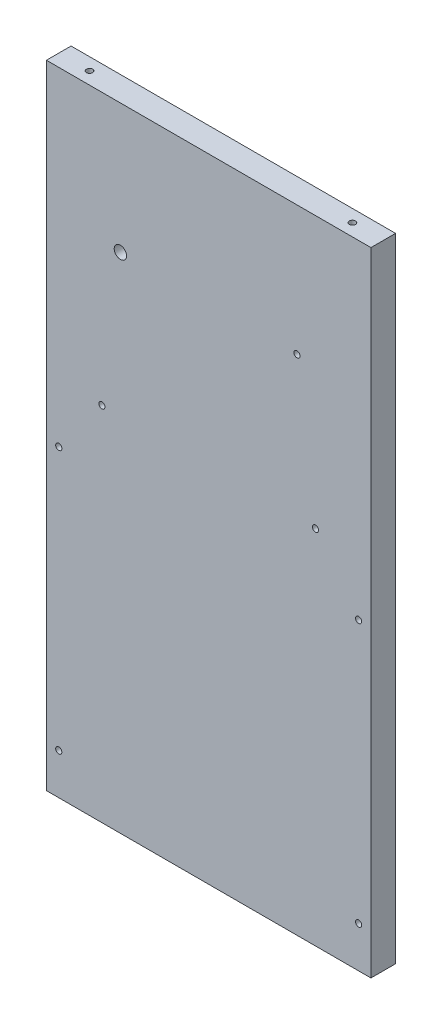
SolidWorks part; units mm, degrees
ref_plane "Front Plane" through (0, 0, 0) normal (0, 0, 1) x (1, 0, 0)
ref_plane "Top Plane" through (0, 0, 0) normal (0, 1, 0) x (1, 0, 0)
ref_plane "Right Plane" through (0, 0, 0) normal (1, 0, 0) x (0, 0, -1)
sketch "Sketch1" plane through (0, 0, 0) normal (0, 0, 1) x (1, 0, 0)
  line L0 (-156.9512, -28.4634) -> (1.0488, -28.4634) construction
  line L1 (-156.9512, 103.5366) -> (1.0488, 103.5366)
  line L2 (-156.9512, 103.5366) -> (-156.9512, -204.4634)
  line L3 (-156.9512, -204.4634) -> (1.0488, -204.4634)
  line L4 (1.0488, 103.5366) -> (1.0488, -204.4634)
  circle A0 centre (-129.9512, -28.4634) radius 1.5
  circle A1 centre (-25.9512, -28.4634) radius 1.5
  circle A2 centre (-34.9512, 40.5366) radius 1.5
  circle A3 centre (-4.9512, -184.4634) radius 1.5
  circle A4 centre (-4.9512, -56.4634) radius 1.5
  circle A5 centre (-150.9512, -184.4634) radius 1.5
  circle A6 centre (-150.9512, -56.4634) radius 1.5
  circle A7 centre (-120.9512, 40.5366) radius 3
  dimension "D4" = 3
  dimension "D5" = 3
  dimension "D8" = 3
  dimension "D11" = 3
  dimension "D12" = 3
  dimension "D17" = 3
  dimension "D18" = 3
  dimension "D23" = 6
  dimension "D1" = 308
  dimension "D2" = 158
  dimension "D3" = 132
  dimension "D6" = 27
  dimension "D7" = 27
  dimension "D9" = 63
  dimension "D10" = 122
  dimension "D13" = 6
  dimension "D14" = 6
  dimension "D15" = 20
  dimension "D16" = 148
  dimension "D19" = 6
  dimension "D20" = 6
  dimension "D21" = 148
  dimension "D22" = 20
  dimension "D24" = 36
  dimension "D25" = 63
extrude "Boss-Extrude1" add sketch "Sketch1" along normal blind 12
sketch "Sketch5" plane through (0, 0, 0) normal (0, 0, 1) x (1, 0, 0)
  circle A0 centre (-25.9512, -28.4634) radius 3
  circle A1 centre (-129.9512, -28.4634) radius 3
  circle A2 centre (-34.9512, 40.5366) radius 3
  circle A3 centre (-4.9512, -56.4634) radius 3
  circle A4 centre (-4.9512, -184.4634) radius 3
  circle A5 centre (-150.9512, -56.4634) radius 3
  circle A6 centre (-150.9512, -184.4634) radius 3
  dimension "D1" = 6
  dimension "D2" = 6
  dimension "D3" = 6
  dimension "D4" = 6
  dimension "D5" = 6
  dimension "D6" = 6
  dimension "D7" = 6
extrude "Cut-Extrude4" cut sketch "Sketch5" along normal blind 3 draft 45 from surface starting at face at (-77.9512, -50.4634, 0)
sketch "Sketch6" plane through (0, 0, 0) normal (0, 1, 0) x (1, 0, 0)
  line L0 (-156.9512, -6) -> (1.0488, -6) construction
  line L1 (-156.9512, -12) -> (-156.9512, 0) construction
  line L2 (1.0488, -12) -> (1.0488, 0) construction
  circle A0 centre (-141.9512, -6) radius 1.5
  circle A1 centre (-13.9512, -6) radius 1.5
  dimension "D3" = 3
  dimension "D4" = 3
  dimension "D1" = 15
  dimension "D2" = 15
extrude "Cut-Extrude5" cut sketch "Sketch6" against normal blind 20 from surface starting at face at (-77.9512, 103.5366, 6)
